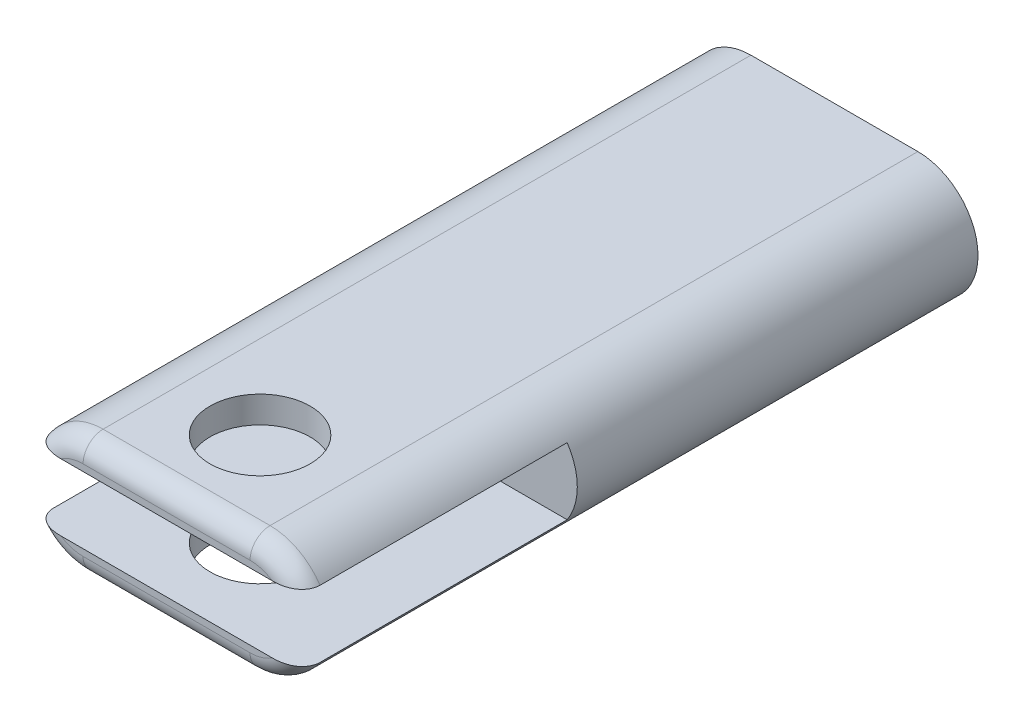
SolidWorks part; units mm, degrees
ref_plane "Front Plane" through (0, 0, 0) normal (0, 0, 1) x (1, 0, 0)
ref_plane "Top Plane" through (0, 0, 0) normal (0, 1, 0) x (1, 0, 0)
ref_plane "Right Plane" through (0, 0, 0) normal (1, 0, 0) x (0, 0, -1)
sketch "Sketch1" plane through (0, 0, 0) normal (0, 0, 1) x (1, 0, 0)
  line L0 (-125, 0) -> (125, 0) construction
  line L1 (-125, 90) -> (125, 90)
  line L2 (-125, -90) -> (125, -90)
  arc A0 (-125, 90) -> (-125, -90) centre (-125, 0) ccw
  arc A1 (125, -90) -> (125, 90) centre (125, 0) ccw
  point P3 (0, 0)
  dimension "D2" = 90
  dimension "D1" = 250
extrude "Boss-Extrude1" add sketch "Sketch1" along normal blind 1000
sketch "Sketch2" plane through (0, 0, 1000) normal (0, 0, 1) x (1, 0, 0)
  line L0 (0, -50) -> (0, 50) construction
  line L10 (215.603, 50) -> (-215.7854, 50)
  line L11 (215.603, 50) -> (215.603, -50)
  line L12 (215.603, -50) -> (-215.7854, -50)
  line L13 (-215.7854, 50) -> (-215.7854, -50)
  point P3 (0, 0)
  dimension "D1" = 100
fillet "Fillet1" radius 30 4 edges at (-215, 0, 1000) (215, 0, 1000) (0, 90, 1000) (0, -90, 1000)
extrude "Cut-Extrude1" cut sketch "Sketch2" against normal blind 400
sketch "Sketch3" plane through (0, 90, 0) normal (0, 1, 0) x (1, 0, 0)
  line L0 (125, -1000) -> (-125, -1000) construction
  circle A0 centre (0, -860) radius 75
  dimension "D1" = 150
  dimension "D2" = 140
extrude "Cut-Extrude2" cut sketch "Sketch3" against normal through all
